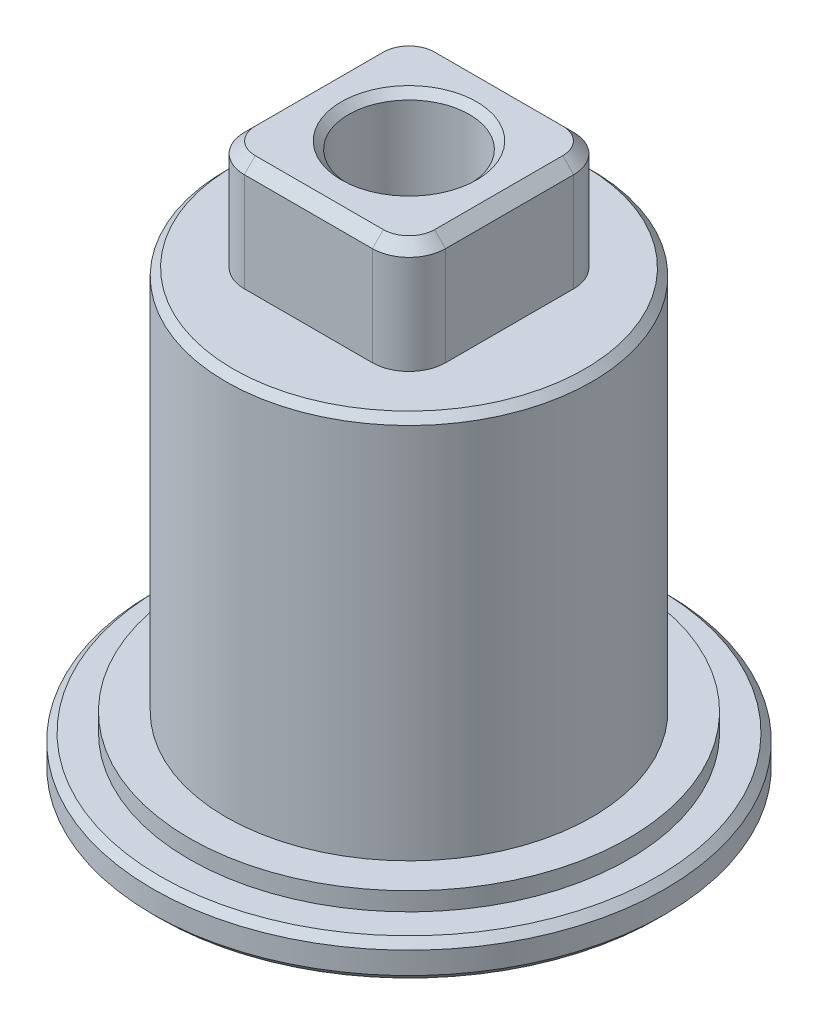
SolidWorks part; units mm, degrees
material "보통 탄소강"
ref_plane "정면" through (0, 0, 0) normal (0, 0, 1) x (1, 0, 0)
ref_plane "윗면" through (0, 0, 0) normal (0, 1, 0) x (1, 0, 0)
ref_plane "우측면" through (0, 0, 0) normal (1, 0, 0) x (0, 0, -1)
sketch "스케치1" plane through (0, 0, 0) normal (0, 1, 0) x (1, 0, 0)
  line L1 (-2.75, -2.75) -> (2.75, -2.75)
  line L2 (-2.75, -2.75) -> (-2.75, 2.75)
  line L3 (-2.75, 2.75) -> (2.75, 2.75)
  line L4 (2.75, -2.75) -> (2.75, 2.75)
  line L5 (-2.75, -2.75) -> (2.75, 2.75) construction
  line L6 (-2.75, 2.75) -> (2.75, -2.75) construction
  circle A0 centre (0, 0) radius 7
  circle A1 centre (0, 0) radius 6
  circle A2 centre (0, 0) radius 5
  circle A3 centre (0, 0) radius 4.25
  circle A5 centre (0, 0) radius 1.65
  dimension "D1" = 14
  dimension "D2" = 12
  dimension "D3" = 10
  dimension "D4" = 8.5
  dimension "D5" = 5.5
  dimension "D6" = 3.3
  dimension "D7" = 5.5
extrude "보스-돌출1" add sketch "스케치1" along normal blind 1 contours A0 A1 | A1 A2 | A2 A3 | A3 | A5 region at (-2.6722, 0, 0) region at (-6.802, 0, 0) region at (-5.8303, 0, 0) region at (-4.8586, 0, 0) region at (-4.1298, 0, 0)
extrude "보스-돌출2" add sketch "스케치1<4>" along normal blind 1.5 contours A1 A2 | A2 A3 | A3 | A5 region at (-2.6722, 0, 0) region at (-5.8303, 0, 0) region at (-4.8586, 0, 0) region at (-4.1298, 0, 0)
sketch "스케치1<4>" plane through (0, 0, 0) normal (0, 1, 0) x (1, 0, 0) same geometry as "스케치1"
extrude "보스-돌출3" add sketch "스케치1<5>" along normal blind 12 contours A2 A3 | A3 | A5 region at (-2.6722, 0, 0) region at (-4.8586, 0, 0) region at (-4.1298, 0, 0)
sketch "스케치1<5>" plane through (0, 0, 0) normal (0, 1, 0) x (1, 0, 0) same geometry as "스케치1"
extrude "보스-돌출4" add sketch "스케치1<6>" along normal blind 10 from offset 2 contours A3 region at (-4.1298, 0, 0)
sketch "스케치1<6>" plane through (0, 0, 0) normal (0, 1, 0) x (1, 0, 0) same geometry as "스케치1"
extrude "보스-돌출5" add sketch "스케치1<7>" along normal blind 13 from offset 2 contours A5 region at (-2.6722, 0, 0)
sketch "스케치1<7>" plane through (0, 0, 0) normal (0, 1, 0) x (1, 0, 0) same geometry as "스케치1"
extrude "보스-돌출6" add sketch "스케치1<8>" along normal blind 2 contours A5 region at (0, 0, 0)
sketch "스케치1<8>" plane through (0, 0, 0) normal (0, 1, 0) x (1, 0, 0) same geometry as "스케치1"
sketch "스케치2" plane through (0, 0, 0) normal (0, -1, 0) x (1, 0, 0)
  line L1 (-1, -4) -> (1, -4)
  line L2 (-1, -4) -> (-1, 4)
  line L3 (-1, 4) -> (1, 4)
  line L4 (1, -4) -> (1, 4)
  line L5 (-1, -4) -> (1, 4) construction
  line L6 (-1, 4) -> (1, -4) construction
  circle A0 centre (0, 3) radius 1
  circle A1 centre (0, -3) radius 1
  point P0 (0, 0)
  dimension "D1" = 8
  dimension "D2" = 2
extrude "컷-돌출1" cut sketch "스케치2" against normal blind 2 contours A1 | A1 L4 A0 L2 | A0 region at (0, 0, -3) region at (0, 0, 0) region at (0, 0, 3)
fillet "필렛1" radius 1 4 edges at (2.75, 13.5, 2.75) (2.75, 13.5, -2.75) (-2.75, 13.5, -2.75) (-2.75, 13.5, 2.75)
chamfer "모따기1" distance 0.2 angle 45 4 edges at (0, 12, 5) (0, 1, 7) (0, 0, 7) (0, 15, 1.65)
chamfer "모따기2" distance 0.3 angle 45 8 edges at (2.75, 15, 0) (0, 15, 2.75) (-2.75, 15, 0) (0, 15, -2.75) (-2.4571, 15, 2.4571) (2.4571, 15, 2.4571) (-2.4571, 15, -2.4571) (2.4571, 15, -2.4571)
sketch "스케치3" plane through (0, 0, 0) normal (1, 0, 0) x (0, 0, -1)
  line L0 (0, 2) -> (-1.65, 2)
  line L1 (-1.65, 2) -> (0, 1.3165)
  line L2 (0, 11.8) -> (0, 2)
  line L3 (-5, 11.8) -> (5, 11.8) construction
  line L5 (0, 2) -> (0, 1.3165)
  line L7 (1.3124, 2) -> (-1.3124, 2) construction
  dimension "D1" = 67.5
  dimension "D2" = 1.65
revolve "컷-회전1" cut sketch "스케치3" angle 360 about L2 region at (0, 1.7722, 0.55)
